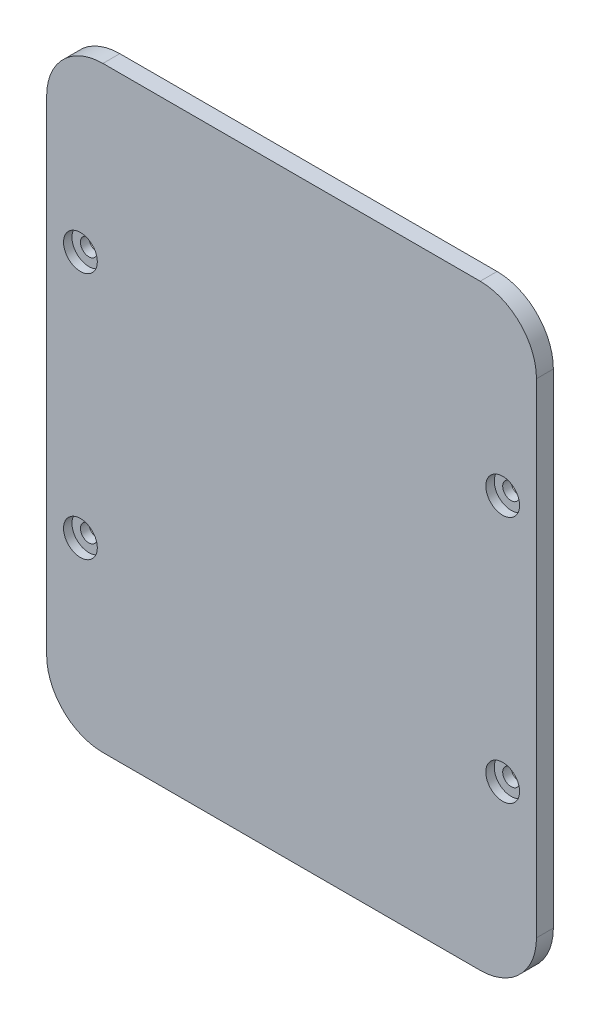
SolidWorks part; units mm, degrees
ref_plane "Front Plane" through (0, 0, 0) normal (0, 0, 1) x (1, 0, 0)
ref_plane "Top Plane" through (0, 0, 0) normal (0, 1, 0) x (1, 0, 0)
ref_plane "Right Plane" through (0, 0, 0) normal (1, 0, 0) x (0, 0, -1)
sketch "Sketch1" plane through (0, 0, 0) normal (0, 0, 1) x (1, 0, 0)
  line L0 (-3, -3) -> (78, -3)
  line L1 (0, 0) -> (75, 0)
  line L2 (0, 0) -> (0, 19)
  line L3 (0, 19) -> (75, 19)
  line L4 (75, 0) -> (75, 19)
  line L5 (78, -3) -> (78, 22)
  line L6 (-3, 22) -> (78, 22)
  line L7 (-3, -3) -> (-3, 22)
  dimension "D1" = 19
  dimension "D2" = 75
  dimension "D3" = 3
extrude "Boss-Extrude1" add sketch "Sketch1" along normal blind 18
sketch "Sketch2" plane through (0, 0, 18) normal (0, 0, 1) x (1, 0, 0)
  line L0 (75, 0) -> (75, 19) construction
  line L1 (20, 29.533) -> (55, 29.533)
  line L2 (20, 29.533) -> (20, -14.7246)
  line L3 (20, -14.7246) -> (55, -14.7246)
  line L4 (55, 29.533) -> (55, -14.7246)
  line L5 (0, 19) -> (0, 0) construction
  dimension "D1" = 20
  dimension "D2" = 20
extrude "Cut-Extrude1" cut sketch "Sketch2" against normal blind 12
sketch "Sketch3" plane through (0, 0, 0) normal (0, 0, -1) x (-1, 0, 0)
  line L1 (3, -3) -> (-78, -3)
  line L2 (3, -3) -> (3, 22)
  line L3 (3, 22) -> (-78, 22)
  line L4 (-78, -3) -> (-78, 22)
extrude "Boss-Extrude2" add sketch "Sketch3" against normal blind 3
fillet "Fillet1" radius 8 2 edges at (37.5, 0, 3) (37.5, 19, 3)
fillet "Fillet2" radius 8 4 edges at (55, 19.6225, 6) (55, -0.6225, 6) (20, -0.6225, 6) (20, 19.6225, 6)
fillet "Fillet3" radius 8 4 edges at (55, 20.5, 18) (20, 20.5, 18) (55, -1.5, 18) (20, -1.5, 18)
sketch "Sketch4" plane through (0, -3, 0) normal (0, -1, 0) x (1, 0, 0)
  line L1 (-3, 0) -> (-33, 0)
  line L2 (-3, 0) -> (-3, 3)
  line L3 (-3, 3) -> (-33, 3)
  line L4 (-33, 0) -> (-33, 3)
  dimension "D1" = 30
  dimension "D2" = 3
extrude "Boss-Extrude3" add sketch "Sketch4" against normal up to surface (25 mm away) up to face at (37.5, 22, 10.8)
sketch "Sketch5" plane through (0, -3, 0) normal (0, -1, 0) x (1, 0, 0)
  line L1 (-3, 3) -> (78, 3)
  line L2 (-3, 3) -> (-3, 0)
  line L3 (-3, 0) -> (78, 0)
  line L4 (78, 3) -> (78, 0)
extrude "Boss-Extrude4" add sketch "Sketch5" along normal blind 25
mirror "Mirror1" about plane through (0, -28, 0) normal (0, -1, 0) of bodies 105
sketch "Sketch6" plane through (0, 0, 3) normal (0, 0, 1) x (1, 0, 0)
  line L0 (-6, -81) -> (-6, 25)
  line L1 (-3, -78) -> (78, -78)
  line L2 (-3, -78) -> (-3, 22)
  line L3 (-3, 22) -> (78, 22)
  line L4 (78, -78) -> (78, 22)
  line L5 (-6, 25) -> (81, 25)
  line L6 (81, -81) -> (81, 25)
  line L7 (-6, -81) -> (81, -81)
  dimension "D1" = 3
extrude "Boss-Extrude6" add sketch "Sketch6" along normal blind 35 and the other way blind 3
sketch "Sketch7" plane through (0, 0, 3) normal (0, 0, 1) x (1, 0, 0)
  line L1 (-6, -81) -> (-52.2418, -81)
  line L2 (-6, -81) -> (-6, 49.2118)
  line L3 (-6, 49.2118) -> (-52.2418, 49.2118)
  line L4 (-52.2418, -81) -> (-52.2418, 49.2118)
extrude "Cut-Extrude2" cut sketch "Sketch7" against normal blind 35
sketch "Sketch8" plane through (0, 0, 3) normal (0, 0, 1) x (1, 0, 0)
  line L0 (-3, 22) -> (-3, -78) construction
  line L1 (31.5, -34) -> (43.5, -34)
  line L2 (31.5, -34) -> (31.5, -22)
  line L3 (31.5, -22) -> (43.5, -22)
  line L4 (43.5, -34) -> (43.5, -22)
  line L5 (28, -73.245) -> (47, -73.245) construction
  point P4 (31.5, -28)
  point P7 (-3, -28)
  point P8 (37.5, -34)
  point P11 (37.5, -73.245)
  dimension "D1" = 12
  dimension "D2" = 12
extrude "Cut-Extrude3" cut sketch "Sketch8" against normal blind 35
sketch "Sketch9" plane through (0, -34, 0) normal (0, 1, 0) x (1, 0, 0)
  line L0 (43.5, 0) -> (43.5, -3) construction
  line L1 (48.5, 0) -> (56.5, 0)
  line L2 (48.5, 0) -> (48.5, 8.9695)
  line L3 (48.5, 8.9695) -> (56.5, 8.9695)
  line L4 (56.5, 0) -> (56.5, 8.9695)
  circle A0 centre (52.5, 4) radius 1.5
  circle A1 centre (52.5, 4) radius 4
  dimension "D1" = 3
  dimension "D2" = 8
  dimension "D3" = 5
extrude "Boss-Extrude7" add sketch "Sketch9" along normal blind 12 contours A1 A0 | A1 L2 L1 | A1 L1 L4 region at (49.3935, -34, -0.8935) region at (55.6065, -34, -0.8935) region at (49.7516, -34, -1.2516)
sketch "Sketch10" plane through (81, 0, 0) normal (1, 0, 0) x (0, 0, -1)
  line L0 (0, -81) -> (-38, -81) construction
  line L1 (0, 25) -> (-38, 25) construction
  circle A0 centre (-19, -41) radius 3
  circle A1 centre (-19, -15) radius 3
  point P4 (0, 0)
  point P7 (-19, -81)
  point P8 (0, 0)
  point P11 (-19, 25)
  dimension "D1" = 6
  dimension "D2" = 6
  dimension "D3" = 40
  dimension "D4" = 40
extrude "Cut-Extrude4" cut sketch "Sketch10" against normal blind 12
sketch "Sketch11" plane through (0, 0, 38) normal (0, 0, 1) x (1, 0, 0)
  line L0 (-3, -53) -> (-3, -3) construction
  line L1 (-3, -9) -> (0, -9)
  line L2 (-3, -9) -> (-3, -3)
  line L3 (-3, -3) -> (3, -3)
  line L4 (3, -6) -> (3, -3)
  line L6 (-3, -3) -> (12.5081, -3) construction
  line L11 (3, -50) -> (3, -53)
  line L12 (-3, -53) -> (3, -53)
  line L13 (-3, -47) -> (-3, -53)
  line L14 (-3, -47) -> (0, -47)
  line L15 (78, -47) -> (75, -47)
  line L16 (78, -47) -> (78, -53)
  line L17 (78, -53) -> (72, -53)
  line L18 (72, -50) -> (72, -53)
  line L19 (72, -6) -> (72, -3)
  line L20 (78, -3) -> (72, -3)
  line L21 (78, -9) -> (78, -3)
  line L22 (78, -9) -> (75, -9)
  circle A0 centre (0, -6) radius 1.5
  arc A5 (0, -9) -> (3, -6) centre (0, -6) ccw
  arc A6 (0, -47) -> (3, -50) centre (0, -50) cw
  circle A7 centre (0, -50) radius 1.5
  circle A8 centre (75, -50) radius 1.5
  arc A9 (75, -47) -> (72, -50) centre (75, -50) ccw
  arc A10 (75, -9) -> (72, -6) centre (75, -6) cw
  circle A11 centre (75, -6) radius 1.5
  point P9 (3, -6)
  point P11 (0, -9)
  dimension "D1" = 3
extrude "Boss-Extrude8" add sketch "Sketch11" against normal blind 10
fillet "Fillet4" radius 6 4 edges at (78, -6, 28) (78, -50, 28) (-3, -50, 28) (-3, -6, 28)
sketch "Sketch12" plane through (0, 0, 38) normal (0, 0, 1) x (1, 0, 0)
  line L1 (-6, -81) -> (81, -81)
  line L2 (-6, -81) -> (-6, 25)
  line L3 (-6, 25) -> (81, 25)
  line L4 (81, -81) -> (81, 25)
  circle A0 centre (0, -50) radius 1.5
  circle A1 centre (0, -6) radius 1.5
  circle A2 centre (75, -6) radius 1.5
  circle A3 centre (75, -50) radius 1.5
extrude "Boss-Extrude9" add sketch "Sketch12" along normal blind 3
sketch "Sketch14" plane through (0, 0, 41) normal (0, 0, 1) x (1, 0, 0)
  circle A0 centre (39.7067, -26.9165) radius 96.2267
extrude "Cut-Extrude5" cut sketch "Sketch14" against normal blind 111 from offset 3 offset against normal yes
sketch "Sketch15" plane through (0, 0, 41) normal (0, 0, 1) x (1, 0, 0)
  circle A0 centre (0, -50) radius 3
  circle A1 centre (0, -6) radius 3
  circle A2 centre (75, -6) radius 3
  circle A3 centre (75, -50) radius 3
  dimension "D1" = 6
  dimension "D2" = 6
  dimension "D3" = 6
  dimension "D4" = 6
extrude "Cut-Extrude6" cut sketch "Sketch15" against normal blind 1.5
fillet "Fillet5" radius 10 4 edges at (81, 25, 39.5) (81, -81, 39.5) (-6, -81, 39.5) (-6, 25, 39.5)
